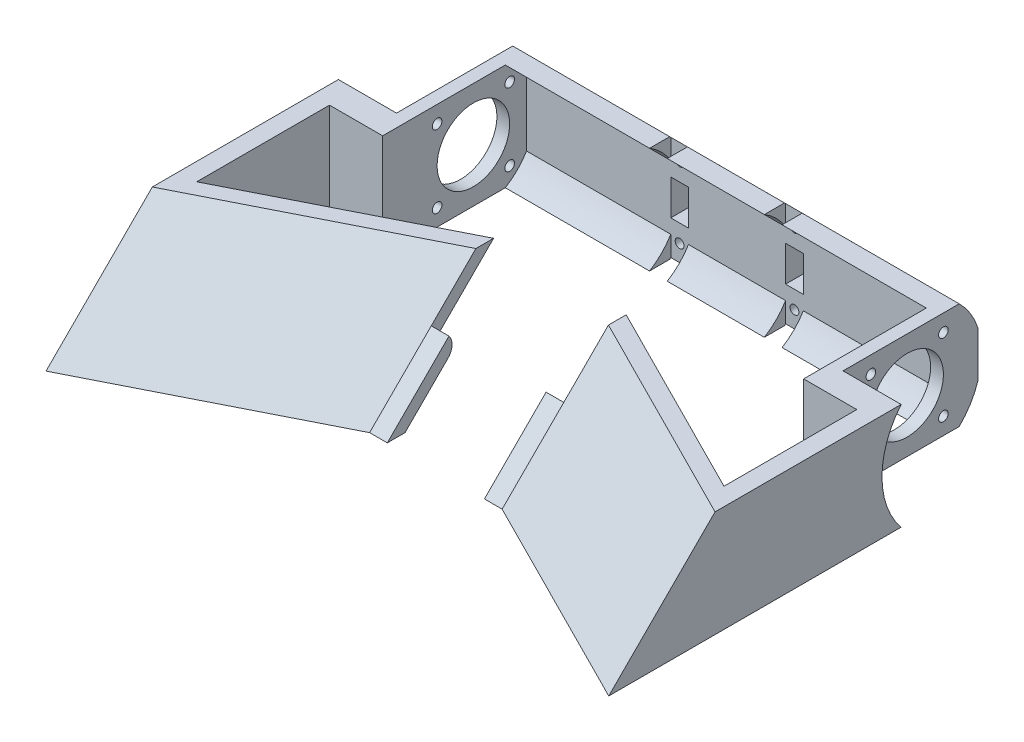
SolidWorks part; units mm, degrees
ref_plane "Front Plane" through (0, 0, 0) normal (0, 0, 1) x (1, 0, 0)
ref_plane "Top Plane" through (0, 0, 0) normal (0, 1, 0) x (1, 0, 0)
ref_plane "Right Plane" through (0, 0, 0) normal (1, 0, 0) x (0, 0, -1)
sketch "Sketch3" plane through (0, 0, 0) normal (0, 1, 0) x (1, 0, 0)
  line L0 (0, 3.175) -> (0, -37.667) construction
  line L1 (-80.01, 3.175) -> (80.01, 3.175)
  line L2 (-80.01, 3.175) -> (-80.01, -3.175)
  line L3 (-80.01, -3.175) -> (80.01, -3.175)
  line L4 (80.01, 3.175) -> (80.01, -3.175)
  line L5 (-80.01, 3.175) -> (80.01, -3.175) construction
  line L6 (-80.01, -3.175) -> (80.01, 3.175) construction
  line L7 (100.838, -54.737) -> (100.838, -48.387)
  line L8 (-80.01, 3.175) -> (-75.438, 3.175)
  line L9 (-80.01, 3.175) -> (-80.01, -54.737)
  line L10 (-80.01, -54.737) -> (-75.438, -54.737)
  line L11 (-75.438, 3.175) -> (-75.438, -54.737)
  line L12 (-75.438, -54.737) -> (-100.838, -54.737)
  line L13 (-75.438, -54.737) -> (-75.438, -48.387)
  line L14 (-75.438, -48.387) -> (-100.838, -48.387)
  line L15 (-100.838, -54.737) -> (-100.838, -48.387)
  line L16 (75.438, -48.387) -> (100.838, -48.387)
  line L17 (75.438, -54.737) -> (75.438, -48.387)
  line L18 (75.438, -54.737) -> (100.838, -54.737)
  line L19 (75.438, 3.175) -> (75.438, -54.737)
  line L20 (80.01, -54.737) -> (75.438, -54.737)
  line L21 (80.01, 3.175) -> (80.01, -54.737)
  point P0 (0, 0)
  dimension "D1" = 6.35
  dimension "D2" = 160.02
  dimension "D3" = 4.572
  dimension "D4" = 57.912
  dimension "D5" = 25.4
  dimension "D6" = 6.35
extrude "Boss-Extrude1" add sketch "Sketch3" along normal blind 38.1 contours L15 L12 L9 L14 | L11 L14 L9 L10 | L14 L11 L3 L9 | L11 L1 L2 L3 | L19 L1 L11 L3 | L1 L19 L3 L4 | L21 L3 L19 L16 | L21 L16 L17 L18 | L16 L21 L18 L7 region at (-77.724, 0, 0) region at (0, 0, 0) region at (-77.724, 0, 25.781) region at (77.724, 0, 0) region at (-77.724, 0, 51.562) region at (-90.424, 0, 51.562) region at (77.724, 0, 25.781) region at (77.724, 0, 51.562) region at (90.424, 0, 51.562)
sketch "Sketch5" plane through (-80.01, 0, 0) normal (-1, 0, 0) x (0, 0, 1)
  line L0 (-3.175, 0) -> (48.387, 0) construction
  line L1 (-3.175, 38.1) -> (-3.175, 0) construction
  circle A0 centre (9.225, 32.05) radius 1.7272
  circle A1 centre (35.225, 32.05) radius 1.7272
  circle A2 centre (35.225, 6.05) radius 1.7272
  circle A3 centre (9.225, 6.05) radius 1.7272
  circle A4 centre (22.225, 19.05) radius 13
  dimension "D7" = 13
  dimension "D8" = 13
  dimension "D1" = 3.4544
  dimension "D2" = 26
  dimension "D3" = 26
  dimension "D4" = 26
  dimension "D5" = 13
  dimension "D6" = 13
  dimension "D9" = 19.05
  dimension "D10" = 13
  dimension "D11" = 25.4
extrude "Cut-Extrude2" cut sketch "Sketch5" against normal through all
sketch "Sketch6" plane through (-80.01, 0, 0) normal (-1, 0, 0) x (0, 0, 1)
  line L0 (22.225, 45.72) -> (-24.9442, 45.72)
  line L1 (-24.9442, 45.72) -> (-24.9442, -7.62)
  line L2 (-24.9442, -7.62) -> (22.225, -7.62)
  arc A0 (22.225, 45.72) -> (22.225, -7.62) centre (22.225, 19.05) ccw
  dimension "D1" = 53.34
extrude "Cut-Extrude3" cut sketch "Sketch6" against normal through all
sketch "Sketch7" plane through (-80.01, 0, 0) normal (-1, 0, 0) x (0, 0, 1)
  line L0 (3.5599, 38.1) -> (10.7774, 38.1)
  line L1 (3.5599, 38.1) -> (48.387, 38.1) construction
  line L2 (-3.175, 27.182) -> (-3.175, 10.918)
  line L3 (3.5599, 0) -> (10.7774, 0)
  arc A0 (10.7774, 38.1) -> (10.7774, 0) centre (22.225, 19.05) ccw
  arc A1 (3.5599, 38.1) -> (-3.175, 27.182) centre (22.225, 19.05) ccw
  arc A2 (-3.175, 10.918) -> (3.5599, 0) centre (22.225, 19.05) ccw
  dimension "D1" = 44.45
extrude "Boss-Extrude2" add sketch "Sketch7" against normal up to surface (155.448 mm away) up to face at (75.438, 32.05, 33.4978)
sketch "Sketch4" plane through (0, 0, 3.175) normal (0, 0, 1) x (1, 0, 0)
  line L0 (0, 0) -> (0, 38.1) construction
  line L1 (-75.438, 38.1) -> (75.438, 38.1) construction
  line L2 (23.749, 12.7) -> (17.399, 25.4) construction
  line L3 (-23.749, 25.4) -> (-17.399, 25.4)
  line L4 (-23.749, 25.4) -> (-23.749, 12.7)
  line L5 (-23.749, 12.7) -> (-17.399, 12.7)
  line L6 (-17.399, 25.4) -> (-17.399, 12.7)
  line L7 (-23.749, 25.4) -> (-17.399, 12.7) construction
  line L8 (-23.749, 12.7) -> (-17.399, 25.4) construction
  line L9 (23.749, 25.4) -> (17.399, 12.7) construction
  line L10 (17.399, 25.4) -> (17.399, 12.7)
  line L11 (23.749, 12.7) -> (17.399, 12.7)
  line L12 (23.749, 25.4) -> (23.749, 12.7)
  line L13 (23.749, 25.4) -> (17.399, 25.4)
  line L14 (-20.574, 19.05) -> (20.574, 19.05)
  line L15 (75.438, 38.1) -> (-75.438, 38.1) construction
  circle A0 centre (-20.574, 31.75) radius 1.5875
  circle A1 centre (-20.574, 6.35) radius 1.5875
  circle A2 centre (20.574, 6.35) radius 1.5875
  circle A3 centre (20.574, 31.75) radius 1.5875
  point P5 (-20.574, 19.05)
  point P14 (20.574, 19.05)
  dimension "D4" = 3.175
  dimension "D1" = 6.35
  dimension "D2" = 12.7
  dimension "D3" = 17.399
  dimension "D5" = 6.35
  dimension "D6" = 19.05
extrude "Cut-Extrude1" cut sketch "Sketch4" against normal through all both and the other way through all contours L6 L3 L4 L5 | A0 | A1 | A3 | L12 L11 L10 L13 | A2 region at (-20.574, 25.258, 3.175)
sketch "Sketch8" plane through (-80.01, 0, 0) normal (-1, 0, 0) x (0, 0, 1)
  circle A0 centre (22.225, 19.05) radius 29.845
  dimension "D1" = 59.69
extrude "Cut-Extrude4" cut sketch "Sketch8" along normal through all contours A0
sketch "Sketch9" plane through (-80.01, 0, 0) normal (-1, 0, 0) x (0, 0, 1)
  line L0 (48.387, 38.1) -> (48.387, 33.4122)
  line L1 (48.387, 38.1) -> (45.1994, 38.1)
  line L3 (48.387, 0) -> (48.387, 4.6878)
  line L4 (48.387, 0) -> (45.1994, 0)
  arc A0 (48.387, 33.4122) -> (45.1994, 38.1) centre (22.225, 19.05) ccw
  arc A1 (45.1994, 0) -> (48.387, 4.6878) centre (22.225, 19.05) ccw
extrude "Boss-Extrude3" add sketch "Sketch9" along normal blind 20.828
mirror "Mirror4" about plane through (0, 0, 0) normal (1, 0, 0) of "Boss-Extrude3", "Cut-Extrude4"
sketch "Sketch10" plane through (0, 0, 3.175) normal (0, 0, 1) x (1, 0, 0)
  line L0 (23.749, 0) -> (17.399, 38.1) construction
  line L3 (0, 30.4976) -> (0, 7.6024) construction
  line L4 (19.5984, 30.4976) -> (-19.5984, 30.4976) construction
  line L5 (-19.5984, 7.6024) -> (19.5984, 7.6024) construction
  line L6 (-23.749, 25.4) -> (-17.399, 12.7) construction
  line L7 (23.749, 38.1) -> (17.399, 0) construction
  line L8 (-23.749, 38.1) -> (-17.399, 38.1)
  line L9 (-23.749, 38.1) -> (-23.749, 0)
  line L10 (-23.749, 0) -> (-17.399, 0)
  line L11 (-17.399, 38.1) -> (-17.399, 0)
  line L12 (-23.749, 38.1) -> (-17.399, 0) construction
  line L13 (-23.749, 0) -> (-17.399, 38.1) construction
  line L14 (23.749, 25.4) -> (17.399, 12.7) construction
  line L15 (17.399, 38.1) -> (17.399, 0)
  line L16 (23.749, 0) -> (17.399, 0)
  line L17 (23.749, 38.1) -> (23.749, 0)
  line L18 (23.749, 38.1) -> (17.399, 38.1)
  point P16 (-20.574, 19.05)
  point P21 (20.574, 19.05)
  dimension "D1" = 6.35
  dimension "D2" = 38.1
extrude "Cut-Extrude5" cut sketch "Sketch10" along normal through all
sketch "Sketch11" plane through (-100.838, 0, 0) normal (-1, 0, 0) x (0, 0, 1)
  line L0 (143.637, 0) -> (105.537, 38.1)
  line L1 (54.737, 38.1) -> (105.537, 38.1)
  line L2 (54.737, 38.1) -> (54.737, 0)
  line L3 (54.737, 0) -> (143.637, 0)
  dimension "D1" = 88.9
  dimension "D2" = 45
  dimension "D3" = 38.1
extrude "Boss-Extrude4" add sketch "Sketch11" against normal blind 6.35
sketch "Sketch12" plane through (0, 0, 0) normal (0, -1, 0) x (1, 0, 0)
  line L0 (-23.749, 10.7774) -> (-23.749, 104.7574) construction
  line L1 (-23.749, 104.7574) -> (-100.838, 143.637)
  dimension "D1" = 93.98
sketch "Sketch13" plane through (-100.838, 0, 0) normal (-1, 0, 0) x (0, 0, 1)
  line L0 (143.637, 0) -> (149.987, 0)
  line L1 (105.537, 38.1) -> (111.887, 38.1)
  line L2 (111.887, 38.1) -> (149.987, 0)
  line L3 (105.537, 38.1) -> (143.637, 0)
  dimension "D1" = 6.35
  dimension "D2" = 6.35
sweep "Sweep1" add profiles "Sketch13" path "Sketch12"
sketch "Sketch17" plane through (-23.749, 0, 0) normal (1, 0, 0) x (0, 0, -1)
  line L1 (-82.6594, 22.098) -> (-104.7574, 0)
  line L2 (-104.7574, 0) -> (-111.1074, 0)
  line L3 (-111.1074, 0) -> (-89.0094, 22.098)
  line L4 (-89.0094, 22.098) -> (-82.6594, 22.098)
  dimension "D1" = 22.098
  dimension "D2" = 45
extrude "Boss-Extrude5" add sketch "Sketch17" along normal blind 6.35
fillet "Fillet1" radius 5.08 1 edges at (-20.574, 22.098, 82.6594)
mirror "Mirror6" about plane through (0, 0, 0) normal (1, 0, 0) of "Fillet1", "Boss-Extrude5", "Sweep1", "Boss-Extrude4"
